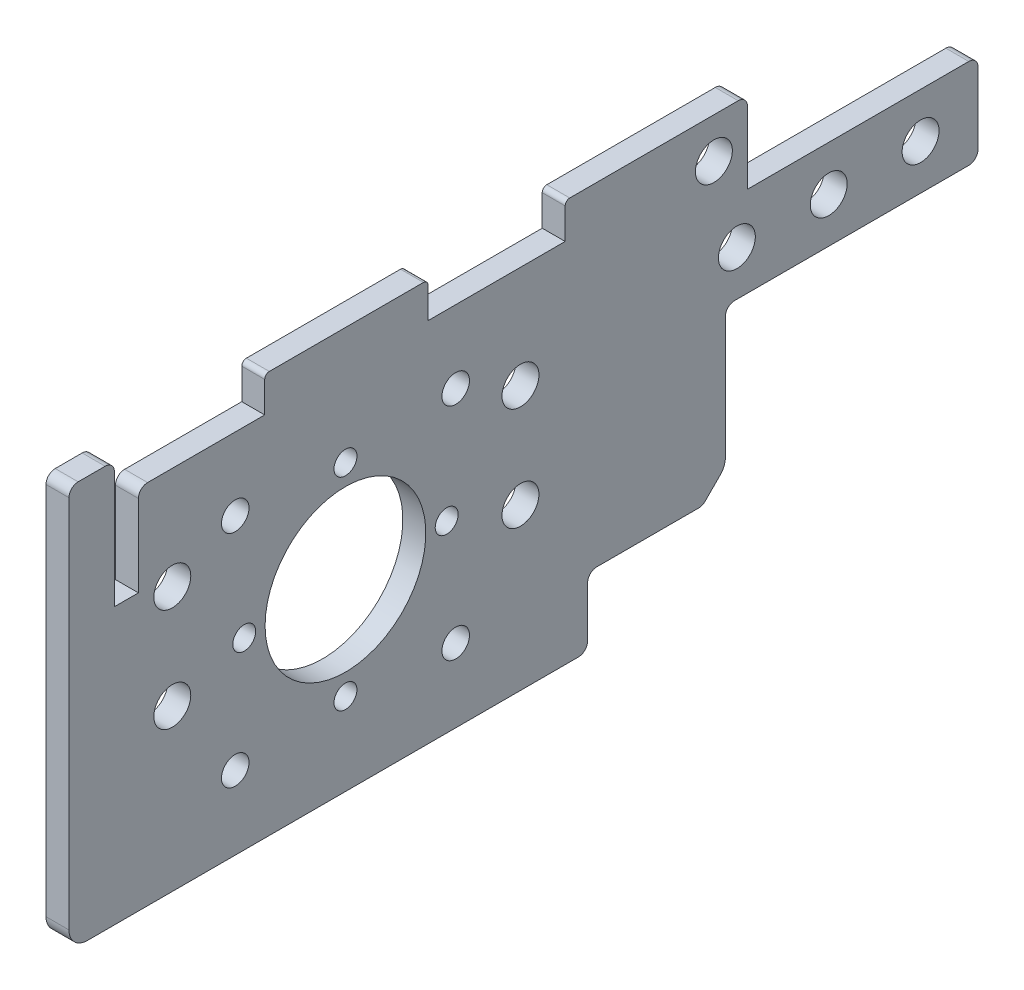
SolidWorks part; units mm, degrees
material "AISI Type A2 Tool Steel"
ref_plane "Front Plane" through (0, 0, 0) normal (0, 0, 1) x (1, 0, 0)
ref_plane "Top Plane" through (0, 0, 0) normal (0, 1, 0) x (1, 0, 0)
ref_plane "Right Plane" through (0, 0, 0) normal (1, 0, 0) x (0, 0, -1)
sketch "Top Layout" plane through (0, 0, 0) normal (0, 1, 0) x (1, 0, 0)
  line L0 (-114.046, -123.825) -> (-104.775, -123.825) construction
  line L1 (-104.775, -142.875) -> (-101.6, -142.875)
  line L2 (-104.775, -142.875) -> (-104.775, -104.775)
  line L3 (-104.775, -104.775) -> (-101.6, -104.775)
  line L4 (-101.6, -142.875) -> (-101.6, -104.775)
  line L5 (-104.775, -142.875) -> (-101.6, -104.775) construction
  line L6 (-104.775, -104.775) -> (-101.6, -142.875) construction
  line L7 (-19.05, -105.8164) -> (-101.6, -105.8164)
  line L8 (-19.05, -105.8164) -> (-19.05, -141.8336)
  line L9 (-19.05, -141.8336) -> (-101.6, -141.8336)
  line L10 (-101.6, -105.8164) -> (-101.6, -141.8336)
  line L11 (-19.05, -105.8164) -> (-101.6, -141.8336) construction
  line L12 (-19.05, -141.8336) -> (-101.6, -105.8164) construction
  line L13 (-133.096, -85.725) -> (-114.046, -85.725)
  line L14 (-133.096, -85.725) -> (-133.096, -161.925)
  line L15 (-133.096, -161.925) -> (-114.046, -161.925)
  line L16 (-114.046, -85.725) -> (-114.046, -161.925)
  line L17 (-133.096, -85.725) -> (-114.046, -161.925) construction
  line L18 (-133.096, -161.925) -> (-114.046, -85.725) construction
  line L19 (-104.775, -123.825) -> (0, -123.825) construction
  line L20 (0, -123.825) -> (0, 0) construction
  line L21 (-52.3528, -40.1717) -> (0, 0) construction
  line L22 (-70.6449, -16.3328) -> (-18.2922, 23.8388)
  line L23 (-34.0606, -64.0105) -> (18.2922, -23.8388)
  line L24 (-30.9251, 40.3023) -> (-122.2248, -29.7544)
  line L25 (-153.9748, -53.975) -> (-153.9748, -123.825)
  line L26 (-109.5248, -162.052) -> (109.5248, -162.052)
  line L27 (0, -162.052) -> (0, -123.825) construction
  line L28 (-109.5248, -162.052) -> (-109.5248, -20.0093) construction
  line L29 (-104.775, -142.875) -> (-104.775, -152.527)
  line L30 (-104.775, -152.527) -> (104.775, -152.527)
  line L31 (104.775, -104.775) -> (101.6, -104.775)
  line L32 (-144.4498, -73.025) -> (-109.5248, -73.025)
  line L33 (-144.4498, -73.025) -> (-144.4498, -123.825)
  line L34 (-144.4498, -123.825) -> (-109.5248, -123.825) construction
  line L35 (-109.5248, -73.025) -> (-109.5248, -162.052)
  line L36 (-144.4498, -73.025) -> (-109.5248, -123.825) construction
  line L37 (-144.4498, -123.825) -> (-109.5248, -73.025) construction
  line L38 (101.6, -142.875) -> (101.6, -104.775)
  line L39 (104.775, -142.875) -> (101.6, -142.875)
  line L40 (104.775, -142.875) -> (104.775, -104.775)
  line L41 (104.775, -142.875) -> (104.775, -152.527)
  line L42 (109.5248, -162.052) -> (109.5248, -20.0093) construction
  line L43 (30.9251, 40.3023) -> (122.2248, -29.7544)
  line L45 (19.05, -141.8336) -> (101.6, -141.8336)
  line L46 (101.6, -105.8164) -> (101.6, -141.8336)
  line L47 (19.05, -105.8164) -> (101.6, -105.8164)
  line L48 (19.05, -105.8164) -> (19.05, -141.8336)
  line L49 (133.096, -161.925) -> (114.046, -161.925)
  line L50 (114.046, -85.725) -> (114.046, -161.925)
  line L51 (133.096, -85.725) -> (114.046, -85.725)
  line L52 (133.096, -85.725) -> (133.096, -161.925)
  line L53 (144.4498, -123.825) -> (109.5248, -123.825) construction
  line L54 (109.5248, -73.025) -> (109.5248, -162.052)
  line L55 (144.4498, -73.025) -> (109.5248, -73.025)
  line L56 (144.4498, -73.025) -> (144.4498, -123.825)
  line L57 (-109.5248, -123.825) -> (-109.5248, -162.052) construction
  line L62 (-153.9748, -53.975) -> (-122.2248, -53.975)
  line L63 (-122.2248, -53.975) -> (-122.2248, -29.7544)
  line L64 (-144.4498, -123.825) -> (-153.9748, -123.825)
  line L65 (153.9748, -53.975) -> (153.9748, -123.825)
  line L66 (109.5248, -123.825) -> (109.5248, -162.052) construction
  line L67 (144.4498, -123.825) -> (153.9748, -123.825)
  line L68 (122.2248, -29.7544) -> (122.2248, -53.975)
  line L73 (-104.775, -104.775) -> (-104.775, -16.3647) construction
  line L74 (-95.25, -162.052) -> (-95.25, -9.0559) construction
  line L75 (-109.5248, -162.052) -> (-109.5248, -123.825) construction
  line L76 (109.5248, -162.052) -> (109.5248, -123.825) construction
  line L77 (122.2248, -53.975) -> (153.9748, -53.975)
  line L83 (104.775, -155.5496) -> (-104.775, -155.5496) construction
  line L88 (95.25, -162.052) -> (95.25, -9.0559) construction
  line L89 (104.775, -104.775) -> (104.775, -16.3647) construction
  line L92 (-104.775, -152.527) -> (-104.775, -162.052) construction
  line L93 (-14.605, -76.327) -> (14.605, -76.327)
  line L94 (-14.605, -76.327) -> (-14.605, -152.527)
  line L95 (-14.605, -152.527) -> (14.605, -152.527)
  line L96 (14.605, -76.327) -> (14.605, -152.527)
  line L97 (-14.605, -76.327) -> (14.605, -152.527) construction
  line L98 (-14.605, -152.527) -> (14.605, -76.327) construction
  line L99 (104.775, -152.527) -> (104.775, -162.052) construction
  line L100 (-19.05, -105.8164) -> (0, -105.8164) construction
  line L107 (0, -105.8164) -> (19.05, -105.8164) construction
  line L108 (104.775, -123.825) -> (114.046, -123.825) construction
  circle A0 centre (0, 0) radius 114.3
  circle A1 centre (0, 0) radius 6.35
  circle A2 centre (-52.3528, -40.1717) radius 17.8
  circle A3 centre (0, 0) radius 30.0482
  circle A4 centre (-52.3528, -40.1717) radius 30.0482
  arc A5 (-30.9251, 40.3023) -> (30.9251, 40.3023) centre (0, 0) cw
  point P2 (-103.1875, -123.825)
  point P7 (-60.325, -123.825)
  point P12 (-123.571, -123.825)
  point P30 (-126.9873, -98.425)
  point P35 (0, -114.427)
  point P53 (0, -152.527)
  dimension "D1" = 35.6
  dimension "D2" = 12.7
  dimension "D3" = 228.6
  dimension "D11" = 60.0964
  dimension "D12" = 50.8
  dimension "D14" = 52.5
  dimension "D4" = 3.175
  dimension "D5" = 19.05
  dimension "D6" = 76.2
  dimension "D7" = 82.55
  dimension "D8" = 38.1
  dimension "D9" = 104.775
  dimension "D10" = 18.0086
  dimension "D13" = 9.525
  dimension "D15" = 4.7498
  dimension "D16" = 9.525
  dimension "D17" = 9.652
  dimension "D18" = 50.8
  dimension "D19" = 12.446
  dimension "D20" = 65.9892
  dimension "D21" = 19.05
  dimension "D22" = 34.925
  dimension "D23" = 123.825
  dimension "D24" = 12.7
  dimension "D25" = 9.525
  dimension "D26" = 29.21
  dimension "D27" = 76.2
  dimension "D28" = 3.0226
sketch "Side Layout" plane through (0, 0, 0) normal (1, 0, 0) x (0, 0, -1)
  line L0 (0, -38.1) -> (0, 33.7344) construction
  line L1 (-114.3, -20.955) -> (114.3, -20.955)
  line L2 (-114.3, -20.955) -> (-114.3, -33.655)
  line L3 (-114.3, -33.655) -> (114.3, -33.655)
  line L4 (114.3, -20.955) -> (114.3, -33.655)
  line L5 (-114.3, -20.955) -> (114.3, -33.655) construction
  line L6 (-114.3, -33.655) -> (114.3, -20.955) construction
  line L7 (-9.525, -32.9406) -> (9.525, -32.9406)
  line L8 (-9.525, -32.9406) -> (-9.525, -38.1)
  line L9 (-9.525, -38.1) -> (9.525, -38.1)
  line L10 (9.525, -32.9406) -> (9.525, -38.1)
  line L11 (-9.525, -32.9406) -> (9.525, -38.1) construction
  line L12 (-9.525, -38.1) -> (9.525, -32.9406) construction
  line L13 (-11.9126, -29.3338) -> (11.9126, -29.3338)
  line L14 (-11.9126, -29.3338) -> (-11.9126, -32.9406)
  line L15 (-11.9126, -32.9406) -> (11.9126, -32.9406)
  line L16 (11.9126, -29.3338) -> (11.9126, -32.9406)
  line L17 (-11.9126, -29.3338) -> (11.9126, -32.9406) construction
  line L18 (-11.9126, -32.9406) -> (11.9126, -29.3338) construction
  line L19 (-6.35, -32.9406) -> (6.35, -32.9406)
  line L20 (-6.35, -32.9406) -> (-6.35, 33.7344)
  line L21 (-6.35, 33.7344) -> (6.35, 33.7344)
  line L22 (6.35, -32.9406) -> (6.35, 33.7344)
  line L23 (-6.35, -32.9406) -> (6.35, 33.7344) construction
  line L24 (-6.35, 33.7344) -> (6.35, -32.9406) construction
  line L25 (-162.052, 0) -> (-123.825, 0) construction
  line L26 (114.3, -33.655) -> (114.3, 0) construction
  line L27 (-142.875, 19.05) -> (-104.775, 19.05)
  line L28 (-40.1717, -9.525) -> (-40.1717, 5.4) construction
  line L29 (-142.875, 19.05) -> (-142.875, -19.05)
  line L30 (-142.875, -19.05) -> (-104.775, -19.05)
  line L31 (-104.775, 19.05) -> (-104.775, -19.05)
  line L32 (-142.875, 19.05) -> (-104.775, -19.05) construction
  line L33 (-142.875, -19.05) -> (-104.775, 19.05) construction
  line L34 (-130.175, -38.1) -> (-117.9516, -38.1) construction
  line L35 (-57.9717, -14.6) -> (-22.3717, -14.6)
  line L36 (-30.0482, -2.794) -> (30.0482, -2.794)
  line L37 (-30.0482, -2.794) -> (-30.0482, -20.955)
  line L38 (-30.0482, -20.955) -> (30.0482, -20.955)
  line L39 (30.0482, -2.794) -> (30.0482, -20.955)
  line L40 (-30.0482, -2.794) -> (30.0482, -20.955) construction
  line L41 (-30.0482, -20.955) -> (30.0482, -2.794) construction
  line L42 (-30.0482, -2.794) -> (-30.0482, 0) construction
  line L43 (-123.825, 0) -> (0, 0) construction
  line L44 (-57.9717, -14.6) -> (-57.9717, 25.4)
  line L45 (-57.9717, 25.4) -> (-22.3717, 25.4)
  line L46 (-22.3717, -14.6) -> (-22.3717, 25.4)
  line L47 (-19.05, 0) -> (19.05, 0)
  line L48 (-19.05, 0) -> (-19.05, -1.9812)
  line L49 (-19.05, -1.9812) -> (19.05, -1.9812)
  line L50 (19.05, 0) -> (19.05, -1.9812)
  line L51 (-19.05, 0) -> (19.05, -1.9812) construction
  line L52 (-19.05, -1.9812) -> (19.05, 0) construction
  line L53 (-70.2199, -3.175) -> (-10.1235, -3.175)
  line L54 (-70.2199, -3.175) -> (-70.2199, -15.875)
  line L55 (-70.2199, -15.875) -> (-10.1235, -15.875)
  line L56 (-10.1235, -3.175) -> (-10.1235, -15.875)
  line L57 (-70.2199, -3.175) -> (-10.1235, -15.875) construction
  line L58 (-70.2199, -15.875) -> (-10.1235, -3.175) construction
  line L59 (-40.1717, -9.525) -> (-40.1717, 0) construction
  line L60 (-57.9717, -14.6) -> (-22.3717, 25.4) construction
  line L61 (-57.9717, 25.4) -> (-22.3717, -14.6) construction
  line L62 (-22.3717, 0) -> (-57.9717, 0) construction
  line L63 (-137.8162, 0) -> (-123.825, -13.9912) construction
  line L64 (-139.065, 15.24) -> (-108.585, 15.24) construction
  line L65 (-139.065, 15.24) -> (-139.065, -15.24) construction
  line L66 (-139.065, -15.24) -> (-108.585, -15.24) construction
  line L67 (-108.585, 15.24) -> (-108.585, -15.24) construction
  line L68 (-139.065, 15.24) -> (-108.585, -15.24) construction
  line L69 (-139.065, -15.24) -> (-108.585, 15.24) construction
  line L70 (-137.8162, 0) -> (-123.825, 13.9912) construction
  line L71 (-123.825, -13.9912) -> (-109.8338, 0) construction
  line L72 (-123.825, 13.9912) -> (-109.8338, 0) construction
  line L73 (-137.8162, 0) -> (-109.8338, 0) construction
  line L74 (-123.825, -13.9912) -> (-123.825, 13.9912) construction
  line L75 (-6.35, 17.8594) -> (6.35, 17.8594)
  line L76 (114.3, 0) -> (-114.3, 0) construction
  line L77 (-22.3717, 19.05) -> (-6.35, 19.05) construction
  line L78 (-123.825, 38.1) -> (-97.9206, 38.1) construction
  line L79 (-19.05, -3.5814) -> (19.05, -3.5814)
  line L80 (-19.05, -3.5814) -> (-19.05, -1.9812)
  line L81 (-19.05, -1.9812) -> (19.05, -1.9812)
  line L82 (19.05, -3.5814) -> (19.05, -1.9812)
  line L83 (-19.05, -3.5814) -> (19.05, -1.9812) construction
  line L84 (-19.05, -1.9812) -> (19.05, -3.5814) construction
  line L85 (-8.7376, -16.7608) -> (8.7376, -16.7608)
  line L86 (-8.7376, -16.7608) -> (-8.7376, -29.3338)
  line L87 (-8.7376, -29.3338) -> (8.7376, -29.3338)
  line L88 (8.7376, -16.7608) -> (8.7376, -29.3338)
  line L89 (-8.7376, -16.7608) -> (8.7376, -29.3338) construction
  line L90 (-8.7376, -29.3338) -> (8.7376, -16.7608) construction
  line L91 (-8.7376, -3.5814) -> (8.7376, -3.5814)
  line L92 (-8.7376, -3.5814) -> (-8.7376, -16.1544)
  line L93 (-8.7376, -16.1544) -> (8.7376, -16.1544)
  line L94 (8.7376, -3.5814) -> (8.7376, -16.1544)
  line L95 (-8.7376, -3.5814) -> (8.7376, -16.1544) construction
  line L96 (-8.7376, -16.1544) -> (8.7376, -3.5814) construction
  circle A0 centre (-123.825, 0) radius 18.0086
  circle A1 centre (-123.825, 0) radius 38.1
  circle A2 centre (-139.065, 15.24) radius 1.905
  circle A3 centre (-108.585, 15.24) radius 1.905
  circle A4 centre (-108.585, -15.24) radius 1.905
  circle A5 centre (-139.065, -15.24) radius 1.905
  circle A6 centre (-137.8162, 0) radius 1.6002
  circle A7 centre (-123.825, 13.9912) radius 1.6002
  circle A8 centre (-109.8338, 0) radius 1.6002
  circle A9 centre (-123.825, -13.9912) radius 1.6002
  point P0 (0, -27.305)
  point P6 (0, -31.1372)
  point P7 (0, -35.5203)
  point P21 (0, 0.3969)
  point P32 (0, -11.8745)
  point P43 (0, -0.9906)
  point P55 (-40.1717, -9.525)
  point P72 (-40.1717, 5.4)
  point P88 (0, -23.0473)
  point P93 (0, -2.7813)
  point P102 (0, -9.8679)
  dimension "D17" = 3.81
  dimension "D18" = 3.2004
  dimension "D1" = 12.7
  dimension "D2" = 5.1594
  dimension "D3" = 19.05
  dimension "D4" = 3.6068
  dimension "D5" = 23.8252
  dimension "D6" = 12.7
  dimension "D7" = 18.161
  dimension "D8" = 1.9812
  dimension "D9" = 12.7
  dimension "D10" = 40
  dimension "D11" = 25.4
  dimension "D12" = 50.8
  dimension "D13" = 41.275
  dimension "D14" = 30.48
  dimension "D15" = 4.445
  dimension "D16" = 19.7866
  dimension "D19" = 15.875
  dimension "D20" = 6.35
  dimension "D21" = 38.1
  dimension "D22" = 1.6002
  dimension "D23" = 38.1
  dimension "D24" = 17.4752
  dimension "D25" = 12.573
ref_plane "Plane1" through (0, 25.4, 0) normal (0, 1, 0) x (1, 0, 0)
sketch "Sketch3" plane through (0, 25.4, 0) normal (0, 1, 0) x (1, 0, 0)
  line L0 (-104.775, -36.3747) -> (-30.9251, 20.2924)
  line L1 (-104.775, -104.775) -> (-104.775, -16.3647) construction
  line L2 (0, -200130.175) -> (0, 199882.0484) construction
  line L3 (-30.9251, 40.3023) -> (-122.2248, -29.7544) construction
  line L5 (-104.775, -36.3747) -> (-104.775, -77.6497)
  line L6 (-92.075, -77.6497) -> (-104.775, -77.6497)
  line L7 (30.9251, 20.2924) -> (104.775, -36.3747)
  line L8 (104.775, -77.6497) -> (92.075, -77.6497)
  line L9 (104.775, -36.3747) -> (104.775, -77.6497)
  line L11 (104.775, -104.775) -> (104.775, -16.3647) construction
  line L12 (30.9251, 40.3023) -> (122.2248, -29.7544) construction
  line L13 (92.075, -74.6536) -> (24.1423, -22.5271)
  line L14 (-32.2514, -66.3682) -> (20.1013, -26.1965)
  line L15 (-30.9251, 20.2924) -> (0, 44.022)
  line L16 (0, 44.022) -> (30.9251, 20.2924)
  line L17 (-92.075, -77.6497) -> (-92.075, -73.1917)
  line L19 (-92.075, -73.1917) -> (-52.3528, -73.1917)
  line L20 (92.075, -74.6536) -> (92.075, -77.6497)
  circle A0 centre (-52.3528, -40.1717) radius 17.8 construction
  circle A1 centre (-52.3528, -40.1717) radius 17.8
  circle A2 centre (0, 0) radius 6.35
  circle A3 centre (0, 0) radius 6.35 construction
  arc A4 (-52.3528, -73.1917) -> (-32.2514, -66.3682) centre (-52.3528, -40.1717) ccw
  arc A5 (20.1013, -26.1965) -> (24.1423, -22.5271) centre (0, 0) ccw
  arc A6 (30.9251, 20.2924) -> (-30.9251, 20.2924) centre (0, -20.01) ccw construction
  point P28 (0, 44.022)
  dimension "D1" = 33.02
  dimension "D5" = 50.8
  dimension "D2" = 41.275
  dimension "D3" = 34.925
  dimension "D4" = 12.7
  dimension "D6" = 38.1
ref_plane "Plane3" through (-104.775, 0, 0) normal (-1, 0, 0) x (0, 0, 1)
sketch "Sketch6" plane through (-104.775, 0, 0) normal (-1, 0, 0) x (0, 0, 1)
  line L0 (162.052, -25.4) -> (162.052, 25.4)
  line L1 (162.052, 25.4) -> (77.6497, 25.4)
  line L2 (36.3747, 25.4) -> (77.6497, 25.4) construction
  line L3 (147.7645, 11.1125) -> (162.052, 11.1125) construction
  line L4 (162.052, 0) -> (71.2997, 0) construction
  line L5 (77.6497, 25.4) -> (77.6497, 19.05)
  line L6 (77.6497, 19.05) -> (36.3747, 19.05)
  line L7 (36.3747, 19.05) -> (36.3747, 6.35)
  line L8 (36.3747, 6.35) -> (71.2997, 6.35)
  line L10 (99.6315, -3.175) -> (99.6315, 11.1125) construction
  line L11 (71.2997, -25.4) -> (162.052, -25.4)
  line L13 (71.2997, 6.35) -> (71.2997, -25.4)
  line L14 (152.527, -25.4) -> (152.527, 25.4) construction
  line L15 (99.6315, 11.1125) -> (99.6315, 25.4) construction
  line L16 (147.7645, 11.1125) -> (147.7645, 25.4) construction
  line L17 (94.869, -7.9375) -> (104.394, -7.9375) construction
  line L18 (94.869, -7.9375) -> (94.869, 25.4) construction
  line L19 (94.869, 25.4) -> (104.394, 25.4) construction
  line L20 (104.394, -7.9375) -> (104.394, 25.4) construction
  line L21 (94.869, -7.9375) -> (104.394, 25.4) construction
  line L22 (94.869, 25.4) -> (104.394, -7.9375) construction
  line L23 (147.7645, 11.1125) -> (147.7645, -3.175) construction
  line L24 (104.394, -7.9375) -> (123.825, -7.9375) construction
  line L25 (143.002, -7.9375) -> (152.527, -7.9375) construction
  line L26 (143.002, -7.9375) -> (143.002, 25.4) construction
  line L27 (143.002, 25.4) -> (152.527, 25.4) construction
  line L28 (152.527, -7.9375) -> (152.527, 25.4) construction
  line L29 (143.002, -7.9375) -> (152.527, 25.4) construction
  line L30 (143.002, 25.4) -> (152.527, -7.9375) construction
  line L31 (123.825, -7.9375) -> (152.527, -7.9375) construction
  line L32 (104.775, 19.05) -> (104.775, -19.05) construction
  line L34 (155.702, -25.4) -> (155.702, 25.4) construction
  circle A0 centre (109.8338, 0) radius 1.6002 construction
  circle A1 centre (123.825, 13.9912) radius 1.6002 construction
  circle A2 centre (137.8162, 0) radius 1.6002 construction
  circle A3 centre (123.825, -13.9912) radius 1.6002 construction
  circle A4 centre (109.8338, 0) radius 1.6002 construction
  circle A5 centre (123.825, 13.9912) radius 1.6002 construction
  circle A6 centre (137.8162, 0) radius 1.6002 construction
  circle A7 centre (123.825, -13.9912) radius 1.6002 construction
  circle A8 centre (123.825, 0) radius 18.0086 construction
  circle A9 centre (123.825, 0) radius 18.0086 construction
  circle A10 centre (123.825, 0) radius 9.525
  circle A11 centre (108.585, -15.24) radius 1.905 construction
  circle A12 centre (108.585, 15.24) radius 1.905 construction
  circle A13 centre (139.065, 15.24) radius 1.905 construction
  circle A14 centre (139.065, -15.24) radius 1.905 construction
  circle A15 centre (108.585, -15.24) radius 1.905
  circle A16 centre (108.585, 15.24) radius 1.905
  circle A17 centre (139.065, 15.24) radius 1.905
  circle A18 centre (139.065, -15.24) radius 1.905
  circle A19 centre (147.7645, 11.1125) radius 2.5527
  circle A26 centre (99.6315, 11.1125) radius 2.5527
  circle A27 centre (99.6315, -3.175) radius 2.5527
  circle A28 centre (147.7645, -3.175) radius 2.5527
  point P29 (0, 0)
  point P55 (99.6315, 8.7312)
  point P61 (147.7645, 8.7312)
  dimension "D4" = 19.05
  dimension "D7" = 5.1054
  dimension "D1" = 6.35
  dimension "D2" = 12.7
  dimension "D3" = 25.4
  dimension "D5" = 6.35
  dimension "D6" = 3.175
  dimension "D8" = 0.381
  dimension "D9" = 14.2875
  dimension "D10" = 9.525
  dimension "D12" = 33.3375
extrude "Side Plate Extrude" add sketch "Sketch6" along normal up to vertex (4.7498 mm away) up to point (-109.5248, 0, 73.025)
sketch "Sketch12" [suppressed] plane through (0, 19.05, 0) normal (0, 1, 0) x (1, 0, 0)
  line L0 (-104.775, -77.6497) -> (-104.775, -36.3747)
  line L1 (-104.775, -36.3747) -> (-92.075, -36.3747)
  line L3 (-92.075, -36.3747) -> (-92.075, -77.6497)
  line L5 (-92.075, -77.6497) -> (-104.775, -77.6497)
  line L6 (-98.425, -77.6497) -> (-98.425, -63.3622) construction
  line L7 (-98.425, -63.3622) -> (-98.425, -50.6622) construction
  line L8 (-98.425, -50.6622) -> (-98.425, -36.3747) construction
  line L10 (-98.425, -36.3747) -> (-104.775, -36.3747) construction
  circle A0 centre (-98.425, -63.3622) radius 2.5527
  circle A1 centre (-98.425, -50.6622) radius 2.5527
  dimension "D2" = 5.1054
  dimension "D1" = 12.7
  dimension "D3" = 12.7
sketch "Sketch15" plane through (-109.5248, 0, 0) normal (-1, 0, 0) x (0, 0, 1)
  line L0 (36.3747, 12.7) -> (44.3122, 12.7) construction
  line L1 (36.3747, 19.05) -> (36.3747, 6.35) construction
  line L2 (44.3122, 12.7) -> (57.0122, 12.7) construction
  line L3 (57.0122, 12.7) -> (69.7122, 12.7) construction
  line L4 (69.7122, 12.7) -> (77.6497, 12.7) construction
  line L5 (77.6497, 12.7) -> (77.6497, 19.05) construction
  circle A0 centre (44.3122, 12.7) radius 2.5527
  circle A1 centre (57.0122, 12.7) radius 2.5527
  circle A2 centre (69.7122, 12.7) radius 2.5527
  dimension "D1" = 5.1054
  dimension "D2" = 12.7
extrude "Custom Nutstrip Holes" cut sketch "Sketch15" against normal through all
ref_plane "Plane5" through (0, 0, 152.527) normal (0, 0, 1) x (1, 0, 0)
sketch "Sketch41" plane through (0, 0, 152.527) normal (0, 0, 1) x (1, 0, 0)
  line L0 (-104.775, -7.9375) -> (-104.775, 25.4) construction
  line L1 (-104.775, -7.9375) -> (-104.775, 12.7)
  line L2 (-104.775, -7.9375) -> (104.775, -7.9375)
  line L3 (104.775, -7.9375) -> (104.775, 12.7)
  line L4 (104.775, 25.4) -> (-104.775, 25.4)
  line L5 (0, -7.9375) -> (0, 25.4) construction
  line L6 (-104.775, 3.9624) -> (-100.0125, 3.9624) construction
  line L7 (-100.0125, 3.9624) -> (-100.0125, 25.4) construction
  line L8 (104.775, 3.9624) -> (100.0125, 3.9624) construction
  line L9 (100.0125, 3.9624) -> (100.0125, 25.4) construction
  line L10 (19.05, 20.6375) -> (23.8252, 20.6375) construction
  line L11 (19.05, 15.875) -> (78.5876, 15.875) construction
  line L12 (19.05, 15.875) -> (19.05, 25.4) construction
  line L13 (19.05, 25.4) -> (78.5876, 25.4) construction
  line L14 (78.5876, 15.875) -> (78.5876, 25.4) construction
  line L15 (19.05, 15.875) -> (78.5876, 25.4) construction
  line L16 (19.05, 25.4) -> (78.5876, 15.875) construction
  line L17 (23.8252, 20.6375) -> (38.1127, 20.6375) construction
  line L18 (38.1127, 20.6375) -> (52.4002, 20.6375) construction
  line L19 (52.4002, 20.6375) -> (66.6877, 20.6375) construction
  line L20 (-104.775, 25.4) -> (-112.395, 25.4)
  line L21 (-112.395, 25.4) -> (-112.395, 3.175)
  line L22 (-112.395, 3.175) -> (-109.5248, 3.175)
  line L23 (-109.5248, 3.175) -> (-109.5248, 12.7)
  line L24 (-109.5248, 12.7) -> (-104.775, 12.7)
  line L25 (-104.775, 12.7) -> (-104.775, 25.4) construction
  line L26 (104.775, 25.4) -> (112.395, 25.4)
  line L27 (112.395, 25.4) -> (112.395, 3.175)
  line L28 (112.395, 3.175) -> (109.5248, 3.175)
  line L29 (109.5248, 3.175) -> (109.5248, 12.7)
  line L30 (109.5248, 12.7) -> (104.775, 12.7)
  line L31 (104.775, 12.7) -> (104.775, 25.4) construction
  line L32 (-100.0125, 3.9624) -> (-87.3125, 3.9624) construction
  line L33 (-63.5, -1.5875) -> (0, -1.5875) construction
  line L34 (0, -1.5875) -> (63.5, -1.5875) construction
  line L35 (63.5, -1.5875) -> (63.5, -7.9375) construction
  circle A0 centre (-100.0125, 3.9624) radius 2.5527
  circle A1 centre (100.0125, 3.9624) radius 2.5527
  circle A2 centre (23.8252, 20.6375) radius 2.5527
  circle A3 centre (38.1127, 20.6375) radius 2.5527
  circle A4 centre (52.4002, 20.6375) radius 2.5527
  circle A5 centre (66.6877, 20.6375) radius 2.5527
  circle A6 centre (-66.6877, 20.6375) radius 2.5527
  circle A7 centre (-52.4002, 20.6375) radius 2.5527
  circle A8 centre (-38.1127, 20.6375) radius 2.5527
  circle A9 centre (-23.8252, 20.6375) radius 2.5527
  circle A10 centre (-87.3125, 3.9624) radius 2.5527
  circle A11 centre (87.3125, 3.9624) radius 2.5527
  circle A12 centre (-63.5, -1.5875) radius 2.5527
  circle A13 centre (63.5, -1.5875) radius 2.5527
  point P14 (48.8188, 20.6375)
  dimension "D3" = 5.1054
  dimension "D7" = 5.1054
  dimension "D1" = 21.4376
  dimension "D2" = 4.7625
  dimension "D4" = 9.525
  dimension "D5" = 59.5376
  dimension "D6" = 4.7752
  dimension "D8" = 14.2875
  dimension "D9" = 7.62
  dimension "D10" = 4.7498
  dimension "D11" = 12.7
  dimension "D12" = 9.525
  dimension "D13" = 19.05
  dimension "D14" = 12.7
  dimension "D15" = 6.35
  dimension "D16" = 63.5
sketch "Sketch43" plane through (-109.5248, 0, 0) normal (-1, 0, 0) x (0, 0, 1)
  line L1 (152.527, 12.7) -> (155.702, 12.7)
  line L2 (152.527, 12.7) -> (152.527, 25.4)
  line L3 (152.527, 25.4) -> (155.702, 25.4)
  line L4 (155.702, 12.7) -> (155.702, 25.4)
  line L5 (152.527, 12.7) -> (155.702, 25.4) construction
  line L6 (152.527, 25.4) -> (155.702, 12.7) construction
  line L7 (162.052, 25.4) -> (77.6497, 25.4) construction
  point P4 (154.1145, 19.05)
  dimension "D1" = 3.175
extrude "Cut-Extrude19" cut sketch "Sketch43" against normal through all
sketch "Sketch44" plane through (0, 25.4, 0) normal (0, 1, 0) x (1, 0, 0)
  line L0 (73.8315, -147.7645) -> (73.8315, -152.527) construction
  line L1 (92.075, -74.6536) -> (92.075, -77.6497) construction
  line L2 (-92.075, -77.6497) -> (-92.075, -73.1917) construction
  line L3 (0, -123.825) -> (0, 0) construction
  line L4 (-92.075, -73.1917) -> (-52.3528, -73.1917) construction
  line L5 (-104.775, -104.775) -> (-104.775, -16.3647) construction
  line L6 (-32.2514, -66.3682) -> (20.1013, -26.1965) construction
  line L21 (-104.775, -68.1247) -> (-104.775, -152.527)
  line L22 (-104.775, -152.527) -> (104.775, -152.527)
  line L23 (104.775, -152.527) -> (104.775, -68.1247)
  line L34 (-104.775, -99.6315) -> (-100.0125, -99.6315) construction
  line L35 (-104.775, -147.7645) -> (-100.0125, -147.7645) construction
  line L36 (0, -152.527) -> (0, -35.6178) construction
  line L38 (30.969, -147.7645) -> (45.2565, -147.7645) construction
  line L39 (45.2565, -147.7645) -> (59.544, -147.7645) construction
  line L40 (59.544, -147.7645) -> (73.8315, -147.7645) construction
  line L41 (23.8252, -152.527) -> (30.969, -152.527) construction
  line L42 (104.775, -152.527) -> (-104.775, -152.527) construction
  line L43 (30.969, -152.527) -> (38.1127, -152.527) construction
  line L44 (30.969, -152.527) -> (30.969, -147.7645) construction
  line L45 (-92.075, -77.6497) -> (-104.775, -77.6497) construction
  line L48 (-35.1507, -62.5899) -> (-8.9743, -42.504) construction
  line L49 (-8.9743, -42.504) -> (17.2021, -22.4182) construction
  line L50 (45.5313, -32.9364) -> (87.3125, -64.9962) construction
  line L51 (92.075, -74.6536) -> (24.1423, -22.5271) construction
  line L52 (104.775, -77.6497) -> (92.075, -77.6497) construction
  line L79 (-104.775, -68.1247) -> (-92.075, -68.1247)
  line L80 (-92.075, -68.1247) -> (-92.075, -63.6667)
  line L85 (21.8118, -8.7328) -> (92.075, -62.6476)
  line L86 (-38.0499, -58.8115) -> (14.3028, -18.6398)
  line L87 (-92.075, -63.6667) -> (-52.3528, -63.6667)
  line L88 (92.075, -62.6476) -> (92.075, -68.1247)
  line L89 (92.075, -68.1247) -> (104.775, -68.1247)
  circle A0 centre (-73.8315, -147.7645) radius 2.5527
  circle A1 centre (-59.544, -147.7645) radius 2.5527
  circle A2 centre (-45.2565, -147.7645) radius 2.5527
  circle A3 centre (-30.969, -147.7645) radius 2.5527
  circle A17 centre (-100.0125, -99.6315) radius 2.5527
  circle A18 centre (-100.0125, -147.7645) radius 2.5527
  circle A19 centre (100.0125, -147.7645) radius 2.5527
  circle A20 centre (100.0125, -99.6315) radius 2.5527
  circle A21 centre (30.969, -147.7645) radius 2.5527
  circle A22 centre (45.2565, -147.7645) radius 2.5527
  circle A23 centre (59.544, -147.7645) radius 2.5527
  circle A24 centre (73.8315, -147.7645) radius 2.5527
  circle A25 centre (-87.3125, -68.4292) radius 4.7625 construction
  circle A26 centre (-35.1507, -62.5899) radius 4.7625 construction
  circle A27 centre (-8.9743, -42.504) radius 4.7625 construction
  circle A28 centre (17.2021, -22.4182) radius 4.7625 construction
  circle A29 centre (45.5313, -32.9364) radius 4.7625 construction
  circle A30 centre (87.3125, -64.9962) radius 4.7625 construction
  circle A32 centre (-87.3125, -68.4292) radius 2.5527
  circle A33 centre (-35.1507, -62.5899) radius 2.5527
  circle A34 centre (-8.9743, -42.504) radius 2.5527 construction
  circle A35 centre (17.2021, -22.4182) radius 2.5527
  circle A36 centre (45.5313, -32.9364) radius 2.5527
  circle A37 centre (87.3125, -64.9962) radius 2.5527
  circle A38 centre (-97.155, -85.2697) radius 7.62 construction
  circle A39 centre (97.155, -85.2697) radius 7.62 construction
  circle A40 centre (24.5121, -32.4156) radius 7.62 construction
  arc A41 (20.1013, -26.1965) -> (24.1423, -22.5271) centre (0, 0) ccw construction
  circle A42 centre (-97.155, -85.2697) radius 2.5527
  circle A43 centre (24.5121, -32.4156) radius 2.5527
  circle A44 centre (97.155, -85.2697) radius 2.5527
  arc A56 (14.3028, -18.6398) -> (21.8118, -8.7328) centre (0, 0) ccw
  arc A57 (-52.3528, -63.6667) -> (-38.0499, -58.8115) centre (-52.3528, -40.1717) ccw
  point P4 (-104.775, -152.527)
  dimension "D2" = 5.1054
  dimension "D7" = 5.1054
  dimension "D8" = 15.24
  dimension "D3" = 9.525
  dimension "D9" = 9.525
  dimension "D4" = 4.7625
  dimension "D5" = 14.2875
  dimension "D6" = 9.525
  dimension "D1" = 4.7625
  dimension "D10" = 52.664
sketch "Sketch72" plane through (0, 25.4, 0) normal (0, 1, 0) x (1, 0, 0)
  line L0 (-104.775, -68.1247) -> (-104.775, -152.527) construction
  line L1 (-104.775, -152.527) -> (-109.5248, -152.527)
  line L2 (-104.775, -152.527) -> (-104.775, -135.0645)
  line L3 (-104.775, -135.0645) -> (-109.5248, -135.0645)
  line L4 (-109.5248, -152.527) -> (-109.5248, -135.0645)
  line L5 (-104.775, -152.527) -> (-109.5248, -135.0645) construction
  line L6 (-104.775, -135.0645) -> (-109.5248, -152.527) construction
  line L7 (-104.775, -152.527) -> (104.775, -152.527) construction
  line L8 (-77.0065, -152.527) -> (-73.8315, -147.7645) construction
  line L9 (-77.0065, -152.527) -> (-27.794, -152.527)
  line L10 (-77.0065, -152.527) -> (-77.0065, -155.5496)
  line L11 (-77.0065, -155.5496) -> (-27.794, -155.5496)
  line L12 (-27.794, -152.527) -> (-27.794, -155.5496)
  line L13 (-77.0065, -152.527) -> (-27.794, -155.5496) construction
  line L14 (-77.0065, -155.5496) -> (-27.794, -152.527) construction
  line L15 (-27.794, -152.527) -> (-30.969, -147.7645) construction
  line L16 (-77.0065, -152.527) -> (-77.0065, -147.7645) construction
  line L18 (-104.775, -93.5247) -> (-109.5248, -93.5247)
  line L19 (-104.775, -93.5247) -> (-104.775, -112.3315)
  line L20 (-104.775, -112.3315) -> (-109.5248, -112.3315)
  line L21 (-109.5248, -93.5247) -> (-109.5248, -112.3315)
  line L22 (-104.775, -93.5247) -> (-109.5248, -112.3315) construction
  line L23 (-104.775, -112.3315) -> (-109.5248, -93.5247) construction
  line L24 (0, -152.527) -> (-12.7, -152.527)
  line L25 (0, -152.527) -> (0, -155.5496)
  line L26 (0, -155.5496) -> (-12.7, -155.5496)
  line L27 (-12.7, -152.527) -> (-12.7, -155.5496)
  line L28 (0, -152.527) -> (-12.7, -155.5496) construction
  line L29 (0, -155.5496) -> (-12.7, -152.527) construction
  line L30 (-104.775, -68.1247) -> (-109.5248, -68.1247)
  line L31 (-104.775, -68.1247) -> (-104.775, -77.6497)
  line L32 (-104.775, -77.6497) -> (-109.5248, -77.6497)
  line L33 (-109.5248, -68.1247) -> (-109.5248, -77.6497)
  line L34 (-104.775, -68.1247) -> (-109.5248, -77.6497) construction
  line L35 (-104.775, -77.6497) -> (-109.5248, -68.1247) construction
  line L38 (-103.505, -155.5496) -> (-90.805, -155.5496)
  line L39 (-90.805, -152.527) -> (-90.805, -155.5496)
  line L40 (-103.505, -155.5496) -> (-103.505, -152.527)
  line L41 (-103.505, -155.5496) -> (-90.805, -152.527) construction
  line L42 (-103.505, -152.527) -> (-90.805, -152.527)
  line L43 (-77.0065, -147.7645) -> (-73.8315, -147.7645) construction
  line L44 (-103.505, -152.527) -> (-101.5221, -149.823) construction
  circle A0 centre (-100.0125, -147.7645) radius 2.5527 construction
  circle A1 centre (-73.8315, -147.7645) radius 2.5527 construction
  circle A2 centre (-30.969, -147.7645) radius 2.5527 construction
  point P4 (-107.1499, -143.7958)
  point P5 (-100.0125, -147.7645)
  point P16 (-52.4002, -154.0383)
  point P18 (-97.155, -154.0383)
  point P25 (-107.1499, -102.9281)
  point P34 (-6.35, -154.0383)
  point P39 (-107.1499, -72.8872)
  dimension "D1" = 4.7498
  dimension "D2" = 12.7
  dimension "D3" = 12.7
  dimension "D4" = 12.7
  dimension "D5" = 9.525
  dimension "D6" = 15.875
  dimension "D7" = 12.7
  dimension "D8" = 3.175
  dimension "D9" = 1.27
  dimension "D10" = 3.0226
sketch "Sketch73" plane through (-109.5248, 0, 0) normal (-1, 0, 0) x (0, 0, 1)
  line L1 (77.6497, 25.4) -> (93.5247, 25.4)
  line L2 (77.6497, 25.4) -> (77.6497, 30.1625)
  line L3 (77.6497, 30.1625) -> (93.5247, 30.1625)
  line L4 (93.5247, 25.4) -> (93.5247, 30.1625)
  line L5 (77.6497, 25.4) -> (93.5247, 30.1625) construction
  line L6 (77.6497, 30.1625) -> (93.5247, 25.4) construction
  line L7 (112.3315, 25.4) -> (135.0645, 25.4)
  line L8 (112.3315, 25.4) -> (112.3315, 30.1625)
  line L9 (112.3315, 30.1625) -> (135.0645, 30.1625)
  line L10 (135.0645, 25.4) -> (135.0645, 30.1625)
  line L11 (112.3315, 25.4) -> (135.0645, 30.1625) construction
  line L12 (112.3315, 30.1625) -> (135.0645, 25.4) construction
  line L13 (155.702, 25.4) -> (162.052, 25.4)
  line L14 (155.702, 25.4) -> (155.702, 30.1625)
  line L15 (155.702, 30.1625) -> (162.052, 30.1625)
  line L16 (162.052, 25.4) -> (162.052, 30.1625)
  line L17 (155.702, 25.4) -> (162.052, 30.1625) construction
  line L18 (155.702, 30.1625) -> (162.052, 25.4) construction
  point P4 (85.5872, 27.7812)
  point P10 (123.698, 27.7812)
  point P16 (158.877, 27.7812)
  dimension "D1" = 4.7625
extrude "Boss-Extrude28" add sketch "Sketch73" against normal through all
sketch "Sketch108" plane through (-104.775, 0, 0) normal (1, 0, 0) x (0, 0, -1)
  line L0 (-93.5247, 30.1625) -> (-77.6497, 30.1625) construction
  line L1 (-77.6497, 19.05) -> (-68.1247, 19.05)
  line L2 (-77.6497, 19.05) -> (-77.6497, 30.1625)
  line L3 (-77.6497, 30.1625) -> (-68.1247, 30.1625)
  line L4 (-68.1247, 19.05) -> (-68.1247, 30.1625)
  line L5 (-77.6497, 19.05) -> (-68.1247, 30.1625) construction
  line L6 (-77.6497, 30.1625) -> (-68.1247, 19.05) construction
  circle A0 centre (-72.8872, 24.6062) radius 2.5527
  circle A1 centre (-69.7122, 12.7) radius 2.5527 construction
  point P4 (-72.8872, 24.6062)
  dimension "D1" = 9.525
extrude "Boss-Extrude35" add sketch "Sketch108" against normal through all
sketch "Sketch90" plane through (-104.775, 0, 0) normal (1, 0, 0) x (0, 0, -1)
  line L0 (-162.052, 30.1625) -> (-155.702, 30.1625) construction
  line L1 (-152.4508, 12.7) -> (-155.7782, 12.7)
  line L2 (-152.4508, 12.7) -> (-152.4508, 25.273)
  line L3 (-152.4508, 30.1625) -> (-155.7782, 30.1625)
  line L4 (-155.7782, 12.7) -> (-155.7782, 30.1625)
  line L5 (-152.4508, 12.7) -> (-155.7782, 30.1625) construction
  line L6 (-152.4508, 30.1625) -> (-155.7782, 12.7) construction
  line L7 (-152.527, 12.7) -> (-155.702, 12.7) construction
  line L8 (-53.8372, 6.477) -> (-53.8372, 6.35) construction
  line L9 (-36.3747, 6.35) -> (-71.2997, 6.35) construction
  line L10 (-135.0645, 30.1625) -> (-112.3315, 30.1625) construction
  line L11 (-152.4508, 30.1625) -> (-134.9883, 30.1625)
  line L12 (-152.4508, 30.1625) -> (-152.4508, 25.273) construction
  line L13 (-152.4508, 25.273) -> (-134.9883, 25.273)
  line L14 (-134.9883, 30.1625) -> (-134.9883, 25.273)
  line L15 (-152.4508, 30.1625) -> (-134.9883, 25.273) construction
  line L16 (-152.4508, 25.273) -> (-134.9883, 30.1625) construction
  line L17 (-112.4077, 30.1625) -> (-93.4485, 30.1625)
  line L18 (-112.4077, 30.1625) -> (-112.4077, 25.273)
  line L19 (-112.4077, 25.273) -> (-93.4485, 25.273)
  line L20 (-93.4485, 30.1625) -> (-93.4485, 25.273)
  line L21 (-112.4077, 30.1625) -> (-93.4485, 25.273) construction
  line L22 (-112.4077, 25.273) -> (-93.4485, 30.1625) construction
  line L23 (-36.3747, 19.05) -> (-36.3747, 6.35) construction
  line L24 (-68.1247, 19.05) -> (-36.3747, 19.05)
  line L25 (-68.1247, 19.05) -> (-68.1247, 18.923) construction
  line L26 (-68.1247, 18.923) -> (-36.3747, 18.923)
  line L27 (-36.3747, 19.05) -> (-36.3747, 18.923)
  line L28 (-68.1247, 19.05) -> (-36.3747, 18.923) construction
  line L29 (-68.1247, 18.923) -> (-36.3747, 19.05) construction
  line L30 (-152.4508, 25.273) -> (-152.4508, 30.1625) construction
  line L31 (-36.3747, 6.477) -> (-71.2997, 6.477)
  line L32 (-36.3747, 6.477) -> (-36.3747, -25.4)
  line L33 (-36.3747, -25.4) -> (-71.2997, -25.4)
  line L34 (-71.2997, 6.477) -> (-71.2997, -25.4)
  line L35 (-36.3747, 6.477) -> (-71.2997, -25.4) construction
  line L36 (-36.3747, -25.4) -> (-71.2997, 6.477) construction
  line L37 (-155.702, 21.4312) -> (-155.7782, 21.4312) construction
  line L38 (-155.702, 12.7) -> (-155.702, 30.1625) construction
  line L39 (-152.527, 19.05) -> (-152.4508, 19.05) construction
  line L40 (-152.527, 25.4) -> (-152.527, 12.7) construction
  line L41 (-143.7196, 25.273) -> (-143.7196, 25.4) construction
  line L42 (-152.527, 25.4) -> (-135.0645, 25.4) construction
  line L43 (-135.0645, 25.4) -> (-134.9883, 25.4) construction
  line L44 (-112.3315, 27.7812) -> (-112.4077, 27.7812) construction
  line L45 (-112.3315, 30.1625) -> (-112.3315, 25.4) construction
  line L46 (-102.9281, 25.4) -> (-102.9281, 25.273) construction
  line L47 (-112.3315, 25.4) -> (-93.5247, 25.4) construction
  line L48 (-93.5247, 25.4) -> (-93.4485, 25.4) construction
  line L49 (-71.2997, -25.4) -> (-162.052, -25.4) construction
  line L50 (-71.2997, 6.35) -> (-71.2997, -25.4) construction
  line L51 (-68.1247, 19.05) -> (-68.1247, 30.1625) construction
  line L52 (-93.5247, 30.1625) -> (-68.1247, 30.1625) construction
  line L53 (-68.2517, 30.1625) -> (-68.1247, 30.1625)
  line L54 (-68.2517, 30.1625) -> (-68.2517, 18.923)
  line L55 (-68.2517, 18.923) -> (-68.1247, 18.923)
  line L56 (-68.1247, 30.1625) -> (-68.1247, 19.05)
  line L57 (-68.2517, 30.1625) -> (-68.1247, 18.923) construction
  line L58 (-68.2517, 18.923) -> (-68.1247, 30.1625) construction
  line L59 (-68.1247, 19.05) -> (-68.1247, 18.923) construction
  point P4 (-154.1145, 21.4312)
  point P10 (-154.1145, 12.7)
  point P17 (-143.7196, 27.7177)
  point P22 (-102.9281, 27.7178)
  point P29 (-52.2497, 18.9865)
  point P37 (-53.8372, -9.4615)
  point P72 (-68.1882, 24.5427)
  dimension "D1" = 0.0762
  dimension "D2" = 0.127
extrude "Side Plate Tolerences" cut sketch "Sketch90" against normal through all
sketch "Sketch111" plane through (-109.5248, 0, 0) normal (-1, 0, 0) x (0, 0, 1)
  circle A0 centre (123.825, 0) radius 11.1125
  dimension "D1" = 22.225
extrude "Cut-Extrude21" cut sketch "Sketch111" against normal through all
sketch "Sketch113" plane through (-109.5248, 0, 0) normal (-1, 0, 0) x (0, 0, 1)
  line L0 (123.825, -13.9954) -> (123.825, 0) construction
  circle A0 centre (123.825, -13.9954) radius 1.5875
  dimension "D2" = 3.175
  dimension "D1" = 13.9954
extrude "Cut-Extrude23" cut sketch "Sketch113" against normal through all
pattern_circular "CirPattern1" count 4 over 360 about axis through (-104.775, 0, 123.825) along (-1, 0, 0) of "Cut-Extrude23"
chamfer "Chamfer8" distance 12.7 1 edges at (-107.1499, -25.4, 71.2997)
fillet "Fillet15" radius 2.54 3 edges at (-107.1499, -12.7, 71.2997) (-107.1499, -25.4, 83.9997) (-107.1499, -25.4, 162.052)
fillet "Fillet26" radius 1.27 7 edges at (-107.1499, 6.477, 36.3747) (-107.1499, 18.923, 36.3747) (-107.1499, 30.1625, 68.2517) (-107.1499, 25.273, 152.4508) (-107.1499, 30.1625, 155.7782) (-107.1499, 30.1625, 162.052) (-107.1499, 6.477, 71.2997)
fillet "Fillet29" radius 0.635 3 edges at (-107.1499, 30.1625, 93.4485) (-107.1499, 30.1625, 112.4077) (-107.1499, 30.1625, 134.9883)
sketch "Sketch109" plane through (-104.775, 0, 0) normal (1, 0, 0) x (0, 0, -1)
  line L0 (-85.0518, -25.4) -> (-159.512, -25.4) construction
  line L1 (-90.3497, -25.4) -> (-71.2997, -25.4)
  line L2 (-90.3497, -25.4) -> (-90.3497, -15.875)
  line L3 (-90.3497, -15.875) -> (-71.2997, -15.875)
  line L4 (-71.2997, -25.4) -> (-71.2997, -15.875)
  line L5 (-90.3497, -25.4) -> (-71.2997, -15.875) construction
  line L6 (-90.3497, -15.875) -> (-71.2997, -25.4) construction
  line L7 (-71.2997, 5.207) -> (-71.2997, -11.6479) construction
  point P4 (-80.8247, -20.6375)
  dimension "D1" = 9.525
  dimension "D2" = 19.05
extrude "Cut-Extrude20" cut sketch "Sketch109" against normal through all
fillet "Fillet30" radius 1.27 3 edges at (-107.1499, -25.4, 90.3497) (-107.1499, -15.875, 90.3497) (-107.1499, -15.875, 74.4747)
sketch "Sketch112" plane through (-109.5248, 0, 0) normal (1, 0, 0) x (0, 0, -1)
  circle A0 centre (-123.825, 0) radius 123.825
extrude "Cut-Extrude22" cut sketch "Sketch112" along normal offset from surface (1.5748 mm away) 3.175 up to face at (-104.775, 1.5875, 137.8204)
